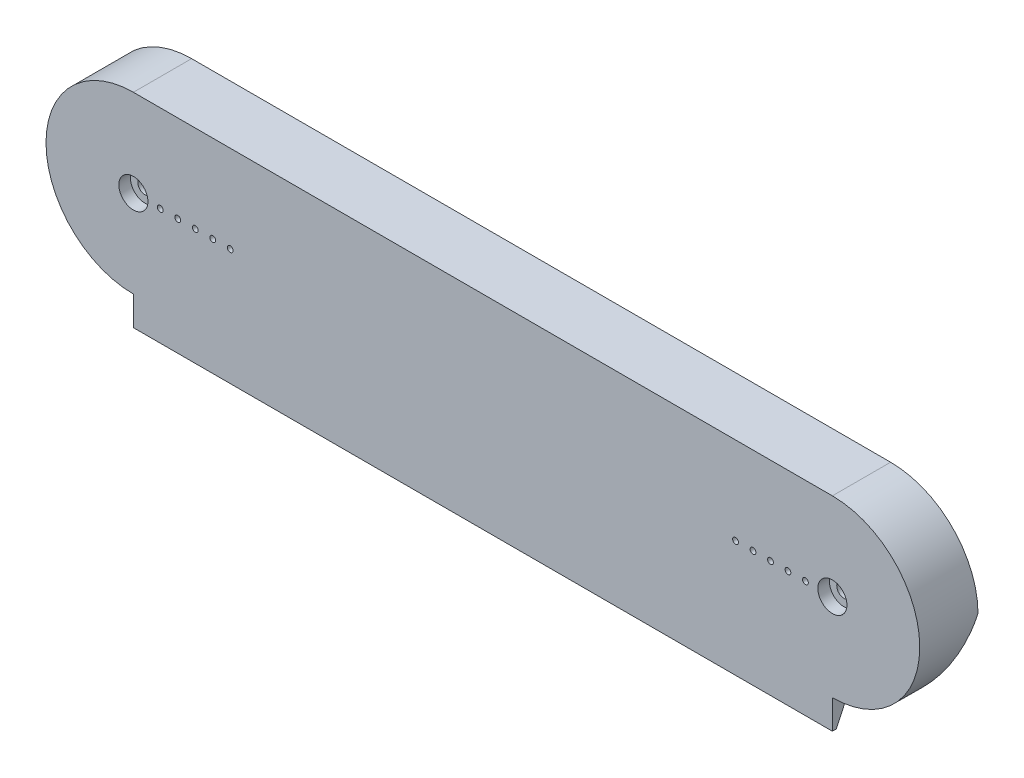
SolidWorks part; units mm, degrees
ref_plane "Front Plane" through (0, 0, 0) normal (0, 0, 1) x (1, 0, 0)
ref_plane "Top Plane" through (0, 0, 0) normal (0, 1, 0) x (1, 0, 0)
ref_plane "Right Plane" through (0, 0, 0) normal (1, 0, 0) x (0, 0, -1)
sketch "Sketch1" plane through (0, 0, 0) normal (0, 0, 1) x (1, 0, 0)
  line L0 (0, 0) -> (120, 0) construction
  line L1 (0, 15) -> (120, 15)
  line L3 (60, 0) -> (60, 50000) construction
  line L5 (0, -15) -> (0, -20)
  line L6 (0, -20) -> (120, -20)
  line L7 (120, -15) -> (120, -20)
  arc A0 (0, 15) -> (0, -15) centre (0, 0) ccw
  arc A1 (120, -15) -> (120, 15) centre (120, 0) ccw
  point P3 (60, 0)
  dimension "D1" = 150
  dimension "D3" = 5
extrude "Boss-Extrude1" add sketch "Sketch1" along normal blind 10
sketch "Sketch2" plane through (0, 0, 0) normal (0, 0, -1) x (-1, 0, 0)
  line L0 (-119.6644, 3.8604) -> (-103.9085, 2.4906)
  line L1 (-59.4954, 13.8593) -> (-59.4954, 50013.8593) construction
  line L2 (-119.6644, -3.8604) -> (-103.9085, -2.4906)
  arc A4 (-119.6644, 3.8604) -> (-119.6644, -3.8604) centre (-120, 0) ccw
  arc A5 (-103.9085, -2.4906) -> (-103.9085, 2.4906) centre (-104.125, 0) ccw
  dimension "D1" = 22.25
  dimension "D2" = 5
  dimension "D3" = 7.75
extrude "Cut-Extrude1" cut sketch "Sketch2" against normal blind 5
sketch "Sketch3" plane through (0, 0, 5) normal (0, 0, -1) x (-1, 0, 0)
  line L0 (-120, 0) -> (49880, 0) construction
  circle A0 centre (-115.375, 0) radius 0.5
  arc A3 (-119.6644, 3.8604) -> (-119.6644, -3.8604) centre (-120, 0) ccw construction
  circle A6 centre (-112.375, 0) radius 0.5
  circle A7 centre (-109.375, 0) radius 0.5
  circle A8 centre (-106.375, 0) radius 0.5
  circle A9 centre (-103.375, 0) radius 0.5
  circle A10 centre (-120, 0) radius 1.25
  dimension "D1" = 1
  dimension "D2" = 8
  dimension "D3" = 5
  dimension "D4" = 2.5
extrude "Cut-Extrude2" cut sketch "Sketch3" against normal up to surface (5 mm away) up to face at (60, -6.6667, 10)
sketch "Sketch5" plane through (0, 0, 10) normal (0, 0, 1) x (1, 0, 0)
  circle A0 centre (120, 0) radius 2.5
  dimension "D1" = 5
extrude "Cut-Extrude3" cut sketch "Sketch5" against normal blind 2
ref_plane "Plane2" through (135, 0, 0) normal (1, 0, 0) x (0, 0, -1)
ref_plane "Plane3" through (60, 0, 0) normal (1, 0, 0) x (0, 0, -1)
mirror "Mirror1" about plane through (60, 0, 0) normal (1, 0, 0) of "Cut-Extrude3", "Cut-Extrude2", "Cut-Extrude1"
chamfer "Chamfer1" distance 20 angle 25 1 edges at (60, -20, 0) first distance on face at (60, -6.6667, 0)
